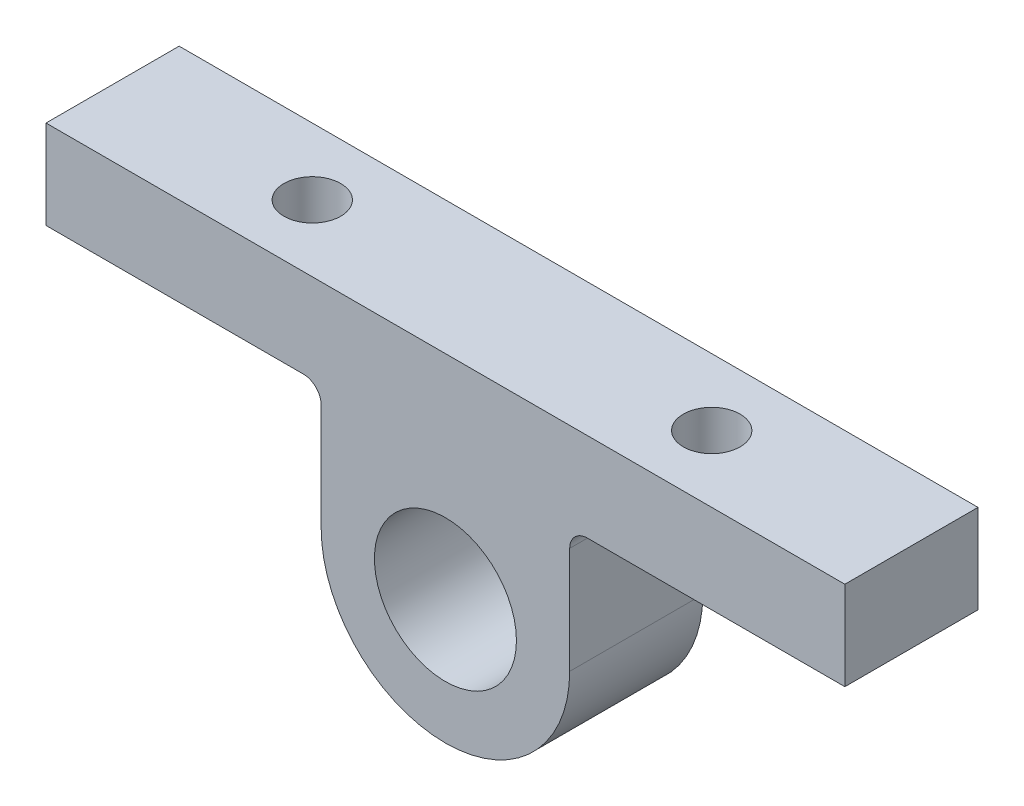
SolidWorks part; units mm, degrees
ref_plane "Alzado" through (0, 0, 0) normal (0, 0, 1) x (1, 0, 0)
ref_plane "Planta" through (0, 0, 0) normal (0, 1, 0) x (1, 0, 0)
ref_plane "Vista lateral" through (0, 0, 0) normal (1, 0, 0) x (0, 0, -1)
sketch "Croquis1" plane through (0, 0, 0) normal (0, 0, 1) x (1, 0, 0)
  line L0 (-14, 0) -> (-14, 14)
  line L1 (-14, 14) -> (-45, 14)
  line L2 (-45, 14) -> (-45, 24)
  line L3 (-45, 24) -> (45, 24)
  line L4 (0, -1000) -> (0, 49000) construction
  line L5 (45, 14) -> (45, 24)
  line L6 (14, 0) -> (14, 14)
  line L7 (14, 14) -> (45, 14)
  circle A0 centre (0, 0) radius 8
  circle A1 centre (0, 0) radius 14
  point P13 (0, 14)
  point P15 (0, 24)
  dimension "D1" = 16
  dimension "D3" = 10
  dimension "D4" = 90
  dimension "D2" = 6
extrude "Saliente-Extruir1" add sketch "Croquis1" along normal mid plane 15 contours A1 L4 L3 L2 L1 L0 | L4 A1 L6 L7 L5 L3 | L4 A1 A0 | A1 L4 A0 region at (-21.5061, 18.3053, 0) region at (-9.6781, 9.6781, 0) region at (9.6781, 9.6781, 0) region at (21.5061, 18.3053, 0)
hole_wizard "Taladro de margen para M61" positions "Croquis2" profile "Croquis3" hole size "M6" standard "ISO"
sketch "Croquis2" plane through (0, 14, 0) normal (0, -1, 0) x (-1, 0, 0)
  line L0 (0, -1000) -> (0, 49000) construction
  point P0 (22.5, 0)
  point P10 (-22.5, 0)
  dimension "D1" = 45
sketch "Croquis3" plane through (-22.5, 14, 0) normal (1, 0, 0) x (0, 0, -1)
  line L0 (0, 0) -> (0, 21.9228)
  line L1 (0, 21.9228) -> (3.2, 20)
  line L2 (3.2, 20) -> (3.2, 0)
  line L5 (3.2, 0) -> (0, 0)
  line L10 (0, 21.9228) -> (-3.2, 20) construction
  line L11 (0, -6.35) -> (0, 107.95) construction
  dimension "Diámetro de taladro" = 6.4
  dimension "Profundidad de taladro" = 20
  dimension "Ángulo de perforador" = 118
fillet "Redondeo1" radius 2 2 edges at (-14, 14, 0) (14, 14, 0)
